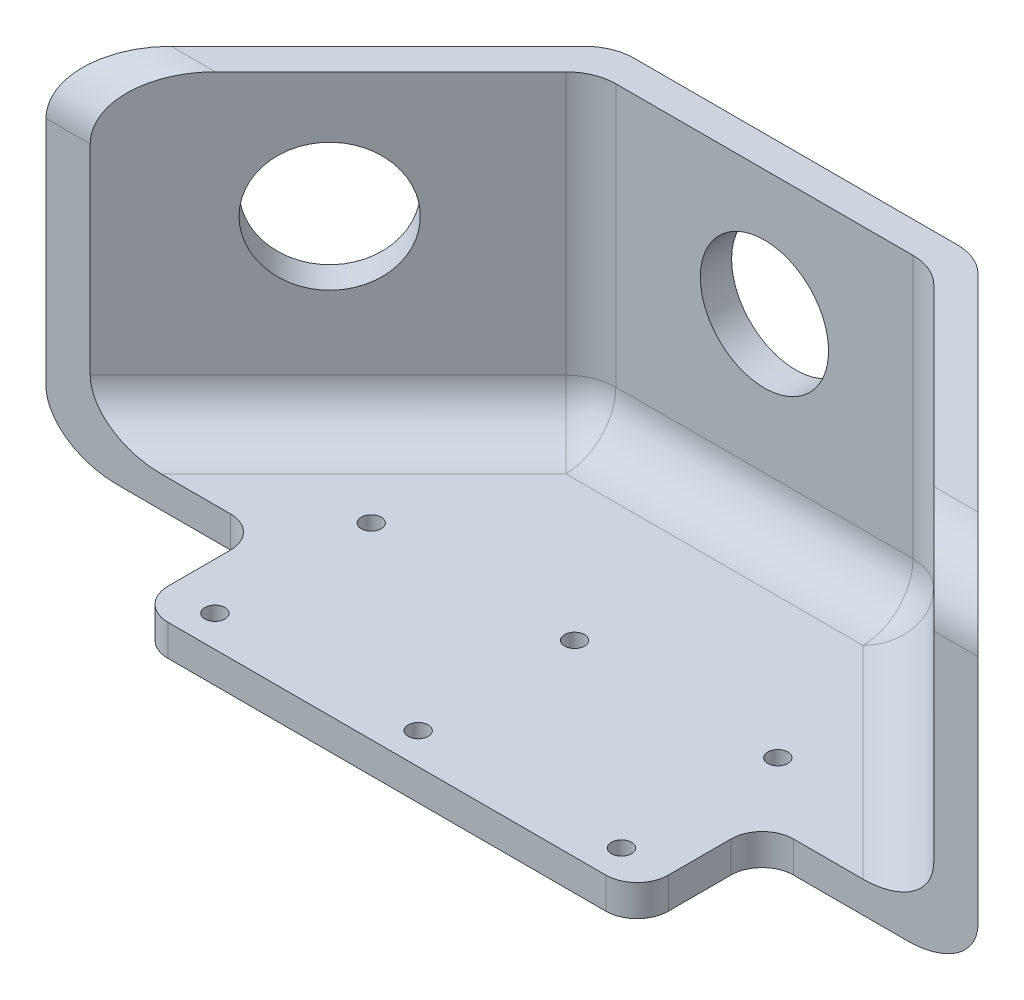
SolidWorks part; units mm, degrees
ref_plane "Front Plane" through (0, 0, 0) normal (0, 0, 1) x (1, 0, 0)
ref_plane "Top Plane" through (0, 0, 0) normal (0, 1, 0) x (1, 0, 0)
ref_plane "Right Plane" through (0, 0, 0) normal (1, 0, 0) x (0, 0, -1)
sketch "Sketch2" plane through (0, 0, 0) normal (0, 1, 0) x (1, 0, 0)
  line L0 (0, 0) -> (120.7107, 0)
  line L1 (120.7107, 0) -> (85.3553, 35.3553)
  line L2 (85.3553, 35.3553) -> (35.3553, 35.3553)
  line L3 (35.3553, 35.3553) -> (0, 0)
  line L4 (31.2132, 45.3553) -> (-24.1421, -10)
  line L5 (-24.1421, -10) -> (144.8528, -10)
  line L6 (144.8528, -10) -> (89.4975, 45.3553)
  line L7 (89.4975, 45.3553) -> (31.2132, 45.3553)
  line L8 (-14.1421, 0) -> (0, 0)
  line L9 (120.7107, 0) -> (134.8528, 0)
  dimension "D1" = 45
  dimension "D2" = 50
  dimension "D3" = 50
  dimension "D4" = 10
extrude "Boss-Extrude1" add sketch "Sketch2" along normal blind 5 contours L1 L9 L6 L7 L4 L8 L3 L2 | L2 L3 L0 L1 region at (60.3553, 0, -15.2369) region at (-7.0711, 0, -1.5575)
sketch "Sketch3" plane through (0, 5, 0) normal (0, 1, 0) x (1, 0, 0)
  line L0 (-14.1421, 0) -> (31.2132, 45.3553)
  line L1 (31.2132, 45.3553) -> (89.4975, 45.3553)
  line L2 (89.4975, 45.3553) -> (134.8528, 0)
  line L3 (-7.0711, 0) -> (33.2843, 40.3553)
  line L4 (33.2843, 40.3553) -> (87.4264, 40.3553)
  line L5 (87.4264, 40.3553) -> (127.7817, 0)
  line L6 (-10.6066, -3.5355) -> (33.2843, 40.3553) construction
  line L7 (87.4264, 40.3553) -> (131.3173, -3.5355) construction
  line L8 (-14.1421, 0) -> (-7.0711, 0)
  line L9 (127.7817, 0) -> (134.8528, 0)
  dimension "D1" = 5
extrude "Boss-Extrude2" add sketch "Sketch3" along normal blind 50
sketch "Sketch5" plane through (0, 0, -45.3553) normal (0, 0, -1) x (-1, 0, 0)
  line L0 (-89.4975, 35) -> (-31.2132, 35)
  line L1 (-89.4975, 55) -> (-89.4975, 0) construction
  line L2 (-31.2132, 55) -> (-31.2132, 0) construction
  line L3 (-89.4975, 55) -> (-31.2132, 55) construction
  circle A0 centre (-60.3553, 35) radius 10.25
  dimension "D1" = 20.5
  dimension "D2" = 20
extrude "Cut-Extrude1" cut sketch "Sketch5" against normal blind 10 contours L0 A0 | L0 A0 region at (60.3553, 39.3502, -45.3553) region at (60.3553, 30.6498, -45.3553)
sketch "Sketch6" plane through (67.4264, 0, -67.4264) normal (0.7071, 0, -0.7071) x (-0.7071, 0, -0.7071)
  line L0 (-95.3553, 35) -> (-31.2132, 35) construction
  line L1 (-95.3553, 55) -> (-95.3553, 0) construction
  line L2 (-31.2132, 55) -> (-31.2132, 0) construction
  line L3 (-95.3553, 55) -> (-31.2132, 55) construction
  circle A0 centre (-63.2843, 35) radius 10.25
  dimension "D1" = 20
  dimension "D2" = 20.5
extrude "Cut-Extrude2" cut sketch "Sketch6" against normal blind 10
sketch "Sketch7" plane through (-7.0711, 0, -7.0711) normal (-0.7071, 0, -0.7071) x (-0.7071, 0, 0.7071)
  line L0 (-54.1421, 35) -> (10, 35) construction
  line L1 (-54.1421, 55) -> (-54.1421, 0) construction
  line L2 (10, 55) -> (10, 0) construction
  line L3 (-54.1421, 55) -> (10, 55) construction
  circle A0 centre (-22.0711, 35) radius 10.25
  dimension "D1" = 20.5
  dimension "D2" = 20
extrude "Cut-Extrude3" cut sketch "Sketch7" against normal blind 10
sketch "Sketch8" plane through (0, 5, 0) normal (0, 1, 0) x (1, 0, 0)
  line L0 (27.8553, 10) -> (92.8553, 10) construction
  line L1 (-7.0711, 0) -> (127.7817, 0) construction
  circle A0 centre (60.3553, 10) radius 1.6
  circle A1 centre (92.8553, 10) radius 1.6
  circle A2 centre (27.8553, 10) radius 1.6
  point P9 (60.3553, 0)
  dimension "D1" = 10
  dimension "D3" = 3.2
  dimension "D2" = 65
extrude "Cut-Extrude4" cut sketch "Sketch8" against normal blind 10
fillet "Fillet1" radius 8 10 edges at (8.5355, 0, -22.6777) (60.3553, 0, -45.3553) (112.1751, 0, -22.6777) (89.4975, 27.5, -45.3553) (13.1066, 5, -20.1777) (33.2843, 30, -40.3553) (107.6041, 5, -20.1777) (87.4264, 30, -40.3553) (31.2132, 27.5, -45.3553) (60.3553, 5, -40.3553)
sketch "Sketch10" plane through (0, 5, 0) normal (0, 1, 0) x (1, 0, 0)
  line L0 (4.2426, 0) -> (116.468, 0) construction
  line L1 (20.3553, 0) -> (100.3553, 0)
  line L2 (20.3553, 0) -> (20.3553, -20)
  line L3 (20.3553, -20) -> (100.3553, -20)
  line L4 (100.3553, 0) -> (100.3553, -20)
  line L5 (84.1127, 32.3553) -> (36.598, 32.3553) construction
  line L6 (27.8553, -15) -> (92.8553, -15) construction
  circle A0 centre (60.3553, -15) radius 1.6
  circle A1 centre (92.8553, -15) radius 1.6
  circle A2 centre (27.8553, -15) radius 1.6
  point P8 (60.3553, 32.3553)
  point P9 (60.3553, -20)
  dimension "D1" = 20
  dimension "D5" = 3.2
  dimension "D2" = 5
  dimension "D3" = 65
  dimension "D4" = 80
extrude "Boss-Extrude5" add sketch "Sketch10" against normal up to surface (5 mm away) up to face at (27.8553, 0, -8.4)
fillet "Fillet4" radius 5 4 edges at (100.3553, 2.5, 20) (100.3553, 2.5, 0) (20.3553, 2.5, 20) (20.3553, 2.5, 0)
fillet "Fillet5" radius 10 2 edges at (131.3173, 55, 0) (-10.6066, 55, 0)
